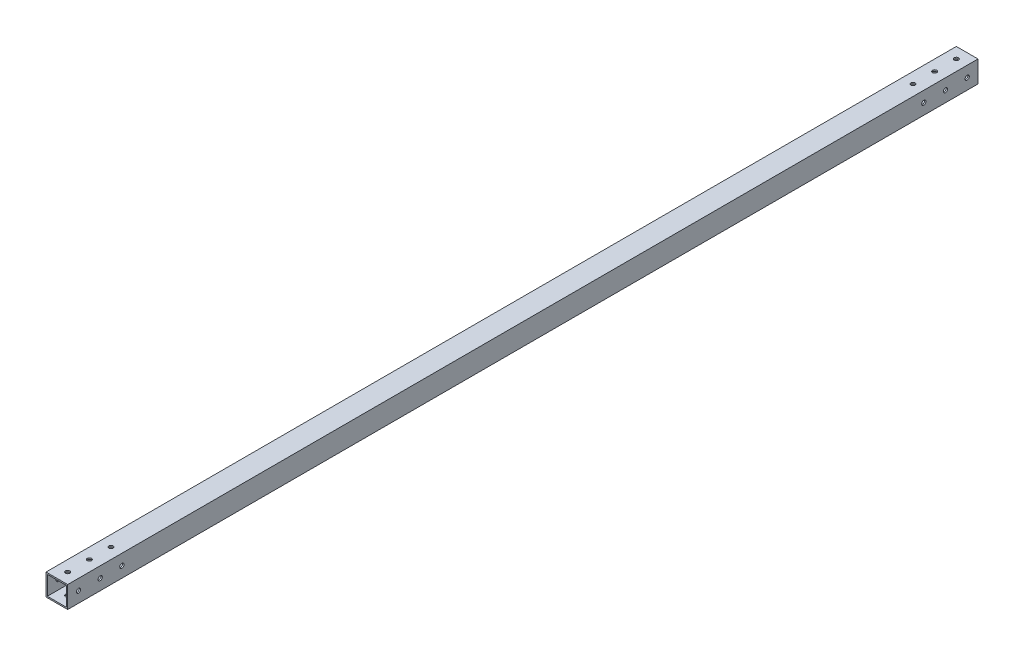
SolidWorks part; units mm, degrees
material "6061-T6 (SS)"
ref_plane "Front Plane" through (0, 0, 0) normal (0, 0, 1) x (1, 0, 0)
ref_plane "Top Plane" through (0, 0, 0) normal (0, 1, 0) x (1, 0, 0)
ref_plane "Right Plane" through (0, 0, 0) normal (1, 0, 0) x (0, 0, -1)
sketch "Sketch1" plane through (0, 0, 0) normal (0, 0, 1) x (1, 0, 0)
  line L1 (0, 0) -> (25.4, 0)
  line L2 (0, 0) -> (0, 25.4)
  line L3 (0, 25.4) -> (25.4, 25.4)
  line L4 (25.4, 0) -> (25.4, 25.4)
  dimension "D1" = 25.4
  dimension "D2" = 25.4
extrude "Boss-Extrude1" add sketch "Sketch1" along normal mid plane 1066.8
shell "Shell1" thickness 1.5875 removed face at (12.7, 12.7, -533.4) removed face at (12.7, 12.7, 533.4)
sketch "Sketch3" plane through (0, 25.4, 0) normal (0, 1, 0) x (1, 0, 0)
  line L0 (25.4, -533.4) -> (0, -533.4) construction
  line L1 (0, -533.4) -> (0, 533.4) construction
  circle A0 centre (12.7, -520.7) radius 2.4892
  circle A1 centre (12.7, -495.3) radius 2.4892
  circle A2 centre (12.7, -469.9) radius 2.4892
  point P10 (0, 0)
  point P11 (0, 0)
  dimension "D1" = 4.9784
  dimension "D2" = 25.4
  dimension "D3" = 25.4
  dimension "D4" = 12.7
  dimension "D5" = 12.7
sketch "Sketch4" plane through (0, 0, 0) normal (-1, 0, 0) x (0, 0, 1)
  line L0 (533.4, 0) -> (-533.4, 0) construction
  line L1 (533.4, 25.4) -> (533.4, 0) construction
  circle A0 centre (520.7, 12.7) radius 2.4892
  circle A1 centre (495.3, 12.7) radius 2.4892
  circle A2 centre (469.9, 12.7) radius 2.4892
  point P8 (0, 0)
  dimension "D1" = 4.9784
  dimension "D2" = 25.4
  dimension "D3" = 25.4
  dimension "D4" = 12.7
  dimension "D5" = 12.7
extrude "Cut-Extrude1" cut sketch "Sketch3" against normal mid plane 1066.8
extrude "Cut-Extrude2" cut sketch "Sketch4" against normal mid plane 1066.8
mirror "Mirror1" about plane through (0, 0, 0) normal (0, 0, 1) of "Cut-Extrude2", "Cut-Extrude1"
